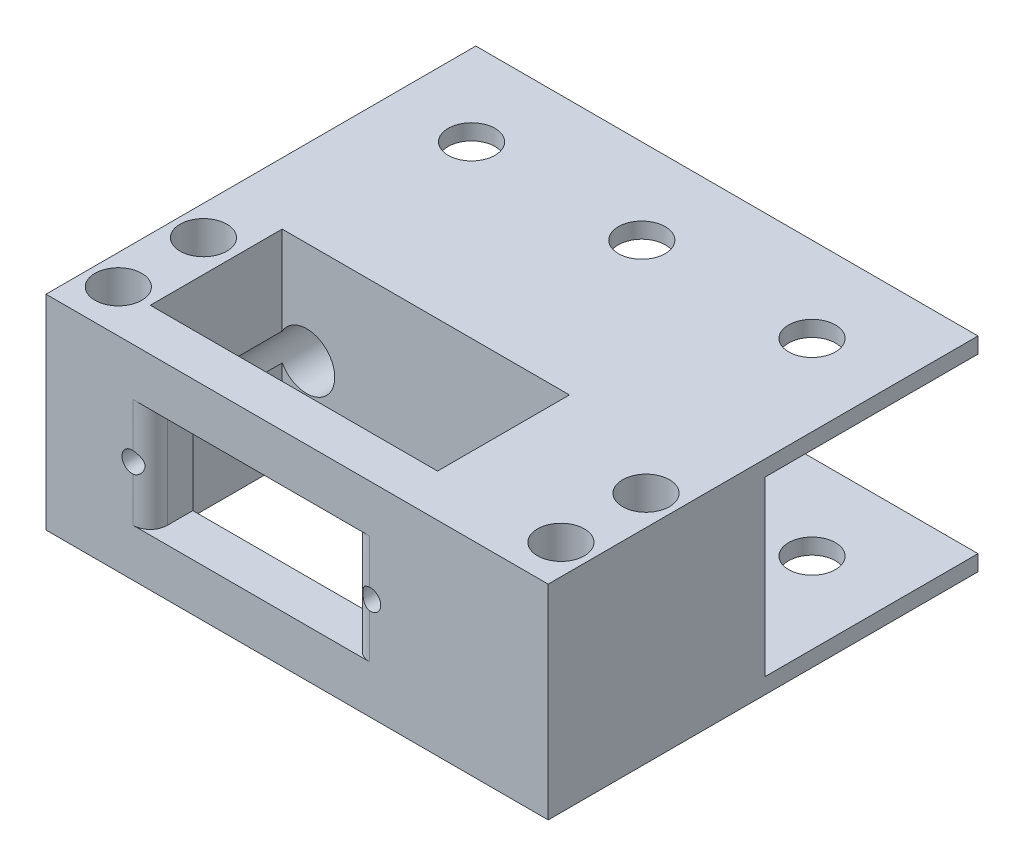
SolidWorks part; units mm, degrees
ref_plane "Front Plane" through (0, 0, 0) normal (0, 0, 1) x (1, 0, 0)
ref_plane "Top Plane" through (0, 0, 0) normal (0, 1, 0) x (1, 0, 0)
ref_plane "Right Plane" through (0, 0, 0) normal (1, 0, 0) x (0, 0, -1)
sketch "Sketch1" plane through (0, 0, 0) normal (0, 0, 1) x (1, 0, 0)
  line L1 (0, 0) -> (59, 0)
  line L2 (0, 0) -> (0, -24)
  line L3 (0, -24) -> (59, -24)
  line L4 (59, 0) -> (59, -24)
  line L5 (36, -18.4) -> (12.25, -18.4)
  line L6 (36, -18.4) -> (36, -5.6)
  line L7 (36, -5.6) -> (12.25, -5.6)
  line L8 (12.25, -18.4) -> (12.25, -5.6)
  line L9 (36, -18.4) -> (12.25, -5.6) construction
  line L10 (36, -5.6) -> (12.25, -18.4) construction
  point P5 (24.125, -12)
  point P10 (0, -12)
  dimension "D1" = 24
  dimension "D2" = 59
  dimension "D3" = 12.8
  dimension "D4" = 23.75
  dimension "D5" = 0
  dimension "D6" = 12.25
extrude "Boss-Extrude1" add sketch "Sketch1" along normal blind 5
sketch "Sketch2" plane through (0, 0, 0) normal (0, 0, -1) x (-1, 0, 0)
  line L0 (-59, 0) -> (0, 0) construction
  line L1 (0, -24) -> (-7.25, -24)
  line L2 (0, -24) -> (0, 0)
  line L3 (0, 0) -> (-7.25, 0)
  line L4 (-7.25, -24) -> (-7.25, 0)
  line L5 (-36, -18.4) -> (-36, -5.6) construction
  line L6 (-59, -24) -> (-41, -24)
  line L7 (-59, -24) -> (-59, 0)
  line L8 (-59, 0) -> (-41, 0)
  line L9 (-41, -24) -> (-41, 0)
  line L10 (-12.25, -5.6) -> (-12.25, -18.4) construction
  dimension "D1" = 5
  dimension "D2" = 5
extrude "Boss-Extrude2" add sketch "Sketch2" along normal blind 15.5
sketch "Sketch3" plane through (0, 0, -15.5) normal (0, 0, -1) x (-1, 0, 0)
  line L1 (0, -24) -> (-59, -24)
  line L2 (0, -24) -> (0, 0)
  line L3 (0, 0) -> (-59, 0)
  line L4 (-59, -24) -> (-59, 0)
extrude "Boss-Extrude3" add sketch "Sketch3" along normal blind 5
sketch "Sketch4" plane through (0, 0, -20.5) normal (0, 0, -1) x (-1, 0, 0)
  line L4 (-59, 0) -> (-59, -24) construction
  line L5 (-118, -22.15) -> (0, -22.15)
  line L6 (-118, -22.15) -> (-118, -1.85)
  line L7 (-118, -1.85) -> (0, -1.85)
  line L8 (0, -22.15) -> (0, -1.85)
  line L9 (-118, -22.15) -> (0, -1.85) construction
  line L10 (-118, -1.85) -> (0, -22.15) construction
  line L11 (0, -24) -> (0, 0) construction
  line L13 (0, 0) -> (-59, 0)
  line L14 (0, 0) -> (0, -24)
  line L15 (0, -24) -> (-59, -24)
  line L16 (-59, 0) -> (-59, -24)
  point P0 (-59, -12)
  line M5 (0, -24) -> (0, 0)
  line M6 (0, 0) -> (-59, 0)
  line M7 (-59, 0) -> (-59, -24)
  line M8 (-59, -24) -> (0, -24)
  dimension "D1" = 20.3
extrude "Boss-Extrude4" add sketch "Sketch4" along normal blind 25 contours L7 M7 M5 M6 | L5 M7 M8 M5
sketch "Sketch5" plane through (0, 0, 0) normal (0, 1, 0) x (1, 0, 0)
  line L0 (0, 45.5) -> (59, 45.5) construction
  circle A0 centre (29.5, 35.5) radius 2.7266
  circle A1 centre (9.5, 35.5) radius 2.6263
  circle A2 centre (49.5, 35.5) radius 2.25
  point P8 (29.5, 45.5)
  dimension "D1" = 20
  dimension "D2" = 20
  dimension "D3" = 0
  dimension "D4" = 10
hole_wizard "M5 Clearance Hole1" positions "Sketch6" profile "Sketch7" hole size "M5" standard "ANSI Metric" end condition through all
sketch "Sketch6" plane through (0, 0, 0) normal (0, 1, 0) x (1, 0, 0)
  point P0 (9.5, 35.5)
  point P3 (29.5, 35.5)
  point P6 (49.5, 35.5)
sketch "Sketch7" plane through (9.5, 0, -35.5) normal (1, 0, 0) x (0, 0, 1)
  line L0 (0, 0) -> (0, 24)
  line L1 (0, 24) -> (2.75, 24)
  line L2 (2.75, 24) -> (2.75, 0)
  line L5 (2.75, 0) -> (0, 0)
  line L11 (0, -6.35) -> (0, 107.95) construction
  dimension "Thru Hole Dia." = 5.5
  dimension "Thru Hole Depth" = 24
sketch "Sketch8" plane through (0, 0, 5) normal (0, 0, 1) x (1, 0, 0)
  line L0 (36, -18.4) -> (36, -5.6) construction
  line L1 (12.25, -5.6) -> (12.25, -18.4) construction
  point P0 (10.125, -12)
  point P1 (38.125, -12)
  dimension "D1" = 2.125
  dimension "D2" = 2.125
hole_wizard "M2 Clearance Hole1" positions "Sketch9" profile "Sketch10" hole size "M2" standard "ANSI Metric"
sketch "Sketch9" plane through (0, 0, 5) normal (0, 0, 1) x (1, 0, 0)
  point P0 (10.125, -12)
  point P3 (38.125, -12)
sketch "Sketch10" plane through (10.125, -12, 5) normal (1, 0, 0) x (0, -1, 0)
  line L0 (0, 0) -> (0, 5)
  line L1 (0, 5) -> (1.2, 5)
  line L2 (1.2, 5) -> (1.2, 0)
  line L5 (1.2, 0) -> (0, 0)
  line L11 (0, -6.35) -> (0, 107.95) construction
  dimension "Thru Hole Dia." = 2.4
  dimension "Thru Hole Depth" = 5
hole_wizard "M6 Clearance Hole2" positions "Sketch15" profile "Sketch17" hole size "M6" standard "ANSI Metric"
sketch "Sketch15" plane through (0, 0, -20.5) normal (0, 0, -1) x (-1, 0, 0)
  point P0 (-38.125, -12)
  point P3 (-10.125, -12)
sketch "Sketch17" plane through (38.125, -12, -20.5) normal (1, 0, 0) x (0, 1, 0)
  line L0 (0, 0) -> (0, 22.4818)
  line L1 (0, 22.4818) -> (3.3, 20.499)
  line L2 (3.3, 20.499) -> (3.3, 0)
  line L5 (3.3, 0) -> (0, 0)
  line L10 (0, 22.4818) -> (-3.3, 20.499) construction
  line L11 (0, -6.35) -> (0, 107.95) construction
  dimension "Hole Dia." = 6.6
  dimension "Hole Depth" = 20.499
  dimension "Drill Angle" = 118
sketch "Sketch18" plane through (0, -24, 0) normal (0, -1, 0) x (1, 0, 0)
  line L0 (59, 5) -> (59, -45.5) construction
  line L1 (0, 5) -> (0, -45.5) construction
  line L2 (0, 5) -> (59, 5) construction
  point P0 (55.5, -10)
  point P1 (55.5, 0)
  point P2 (3.5, -10)
  point P3 (3.5, 0)
  dimension "D1" = 3.5
  dimension "D2" = 3.5
  dimension "D3" = 3.5
  dimension "D4" = 3.5
  dimension "D5" = 15
  dimension "D6" = 5
  dimension "D7" = 0
  dimension "D8" = 0
hole_wizard "M5 Clearance Hole2" positions "Sketch19" profile "Sketch21" hole size "M5" standard "ANSI Metric" end condition through all
sketch "Sketch19" plane through (0, -24, 0) normal (0, -1, 0) x (-1, 0, 0)
  point P0 (-55.5, 10)
  point P3 (-55.5, 0)
  point P6 (-3.5, 10)
  point P9 (-3.5, 0)
sketch "Sketch21" plane through (55.5, -24, -10) normal (1, 0, 0) x (0, 0, -1)
  line L0 (0, 0) -> (0, 24)
  line L1 (0, 24) -> (2.75, 24)
  line L2 (2.75, 24) -> (2.75, 0)
  line L5 (2.75, 0) -> (0, 0)
  line L11 (0, -6.35) -> (0, 107.95) construction
  dimension "Thru Hole Dia." = 5.5
  dimension "Thru Hole Depth" = 24
fillet "Fillet1" radius 2 2 edges at (12.25, -12, 5) (36, -12, 5)
equation "\"railplatescrewoffset\"=3.5"
equation "\"D1@Sketch18\"=\"railplatescrewoffset\""
equation "\"D2@Sketch18\"=\"railplatescrewoffset\""
equation "\"D3@Sketch18\"=\"railplatescrewoffset\""
equation "\"D4@Sketch18\"=\"railplatescrewoffset\""
